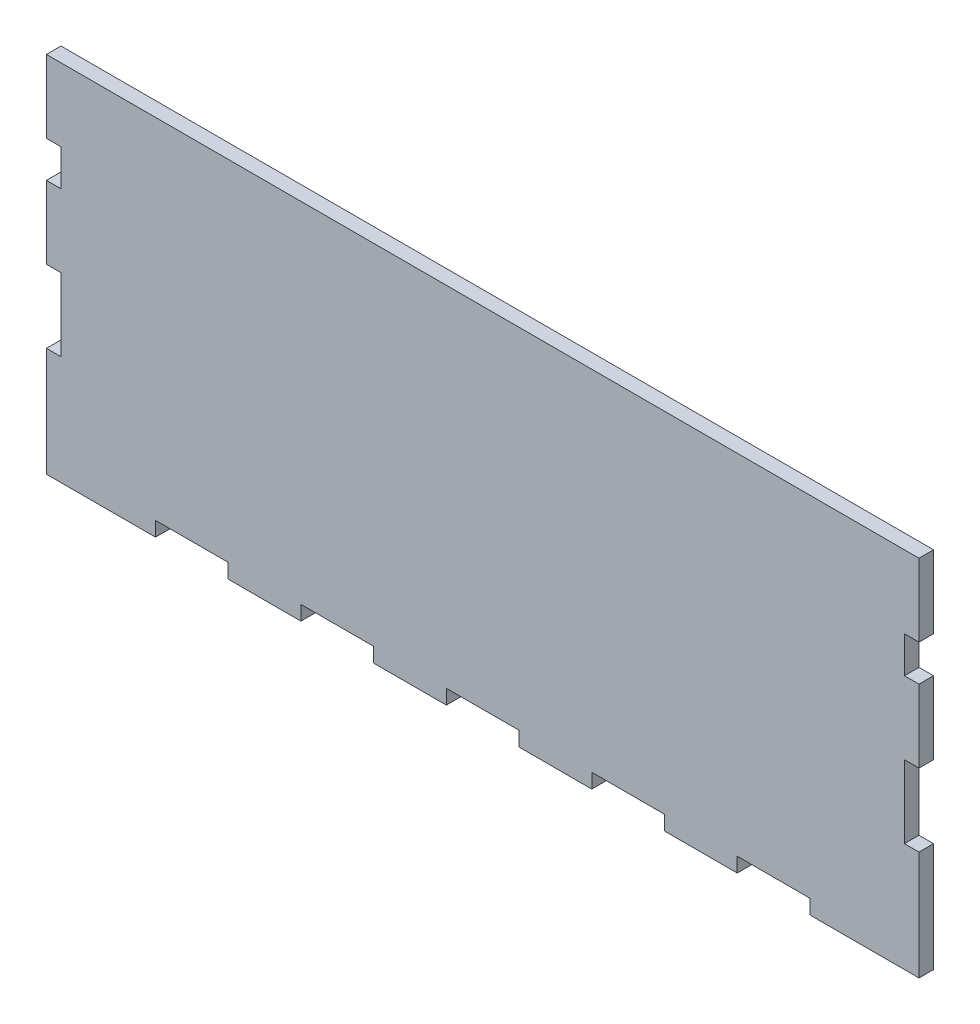
SolidWorks part; units mm, degrees
ref_plane "Front Plane" through (0, 0, 0) normal (0, 0, 1) x (1, 0, 0)
ref_plane "Top Plane" through (0, 0, 0) normal (0, 1, 0) x (1, 0, 0)
ref_plane "Right Plane" through (0, 0, 0) normal (1, 0, 0) x (0, 0, -1)
sketch "Sketch1" plane through (0, 0, 0) normal (0, 0, 1) x (1, 0, 0)
  line L0 (0, 0) -> (0, -127) construction
  line L1 (152.4, 0) -> (-152.4, 0)
  line L2 (12.7, -127) -> (-12.7, -127)
  line L3 (-12.7, -127) -> (-12.7, -121.92)
  line L4 (-12.7, -121.92) -> (-38.1, -121.92)
  line L5 (-38.1, -121.92) -> (-38.1, -127)
  line L6 (-38.1, -127) -> (-63.5, -127)
  line L7 (-63.5, -127) -> (-63.5, -121.92)
  line L8 (-63.5, -121.92) -> (-88.9, -121.92)
  line L9 (-88.9, -121.92) -> (-88.9, -127)
  line L10 (-88.9, -127) -> (-114.3, -127)
  line L11 (-152.4, -127) -> (-152.4, -114.3)
  line L12 (-114.3, -127) -> (-114.3, -121.92)
  line L13 (-114.3, -121.92) -> (-139.7, -121.92)
  line L14 (-139.7, -121.92) -> (-139.7, -127)
  line L15 (-139.7, -127) -> (-152.4, -127)
  line L16 (-152.4, -114.3) -> (-147.32, -114.3)
  line L17 (-147.32, -114.3) -> (-147.32, -88.9)
  line L18 (-147.32, -88.9) -> (-152.4, -88.9)
  line L19 (-152.4, -63.5) -> (-147.32, -63.5)
  line L20 (-147.32, -63.5) -> (-147.32, -38.1)
  line L21 (-147.32, -38.1) -> (-152.4, -38.1)
  line L22 (-152.4, -25.4) -> (-147.32, -25.4)
  line L23 (-147.32, -25.4) -> (-147.32, 0)
  line L24 (-152.4, -88.9) -> (-152.4, -63.5)
  line L25 (-152.4, -38.1) -> (-152.4, -25.4)
  line L26 (152.4, -38.1) -> (152.4, -25.4)
  line L27 (152.4, -88.9) -> (152.4, -63.5)
  line L28 (147.32, -25.4) -> (147.32, 0)
  line L29 (152.4, -25.4) -> (147.32, -25.4)
  line L30 (147.32, -38.1) -> (152.4, -38.1)
  line L31 (147.32, -63.5) -> (147.32, -38.1)
  line L32 (152.4, -63.5) -> (147.32, -63.5)
  line L33 (147.32, -88.9) -> (152.4, -88.9)
  line L34 (147.32, -114.3) -> (147.32, -88.9)
  line L35 (152.4, -114.3) -> (147.32, -114.3)
  line L36 (139.7, -127) -> (152.4, -127)
  line L37 (139.7, -121.92) -> (139.7, -127)
  line L38 (114.3, -121.92) -> (139.7, -121.92)
  line L39 (114.3, -127) -> (114.3, -121.92)
  line L40 (152.4, -127) -> (152.4, -114.3)
  line L41 (88.9, -127) -> (114.3, -127)
  line L42 (88.9, -121.92) -> (88.9, -127)
  line L43 (63.5, -121.92) -> (88.9, -121.92)
  line L44 (63.5, -127) -> (63.5, -121.92)
  line L45 (38.1, -127) -> (63.5, -127)
  line L46 (38.1, -121.92) -> (38.1, -127)
  line L47 (12.7, -121.92) -> (38.1, -121.92)
  line L48 (12.7, -127) -> (12.7, -121.92)
  line L49 (-147.32, 0) -> (147.32, 0)
  line L50 (-152.4, 0) -> (-152.4, -127)
  line L51 (-152.4, -127) -> (152.4, -127)
  line L52 (152.4, -127) -> (152.4, 0)
  line L53 (-147.32, 0) -> (-147.32, -114.3)
  line L54 (-139.7, -121.92) -> (139.7, -121.92)
  line L55 (147.32, 0) -> (147.32, -114.3)
  dimension "D1" = 152.4
  dimension "D2" = 127
  dimension "D3" = 12.7
  dimension "D4" = 25.4
  dimension "D5" = 5.08
  dimension "D6" = 12.7
  dimension "D7" = 25.4
extrude "Boss-Extrude1" add sketch "Sketch1" along normal mid plane 5.08 contours L1 L50 L22 L23 | L21 L50 L19 L20 | L18 L50 L16 L17 | L14 L51 L12 L13 | L9 L51 L7 L8 | L0 L49 L23 L53 L20 L17 L16 L11 L15 L14 L13 L54 L8 L4 | L1 L0 L54 L47 L43 L38 L37 L36 L40 L35 L34 L55 L31 L28 | L5 L51 L3 L4 | L44 L51 L42 L43 | L48 L51 L46 L47 | L39 L51 L37 L38 | L35 L52 L33 L34 | L32 L52 L30 L31 | L29 L52 L1 L28 region at (74.0818, -61.3092, 0) region at (-74.0818, -61.3093, 0) region at (149.86, -12.7, 0) region at (-149.86, -12.7, 0) region at (-25.4, -124.46, 0) region at (25.4, -124.46, 0) region at (149.86, -50.8, 0) region at (-149.86, -50.8, 0) region at (-76.2, -124.46, 0) region at (76.2, -124.46, 0) region at (149.86, -101.6, 0) region at (-149.86, -101.6, 0) region at (-127, -124.46, 0) region at (127, -124.46, 0)
